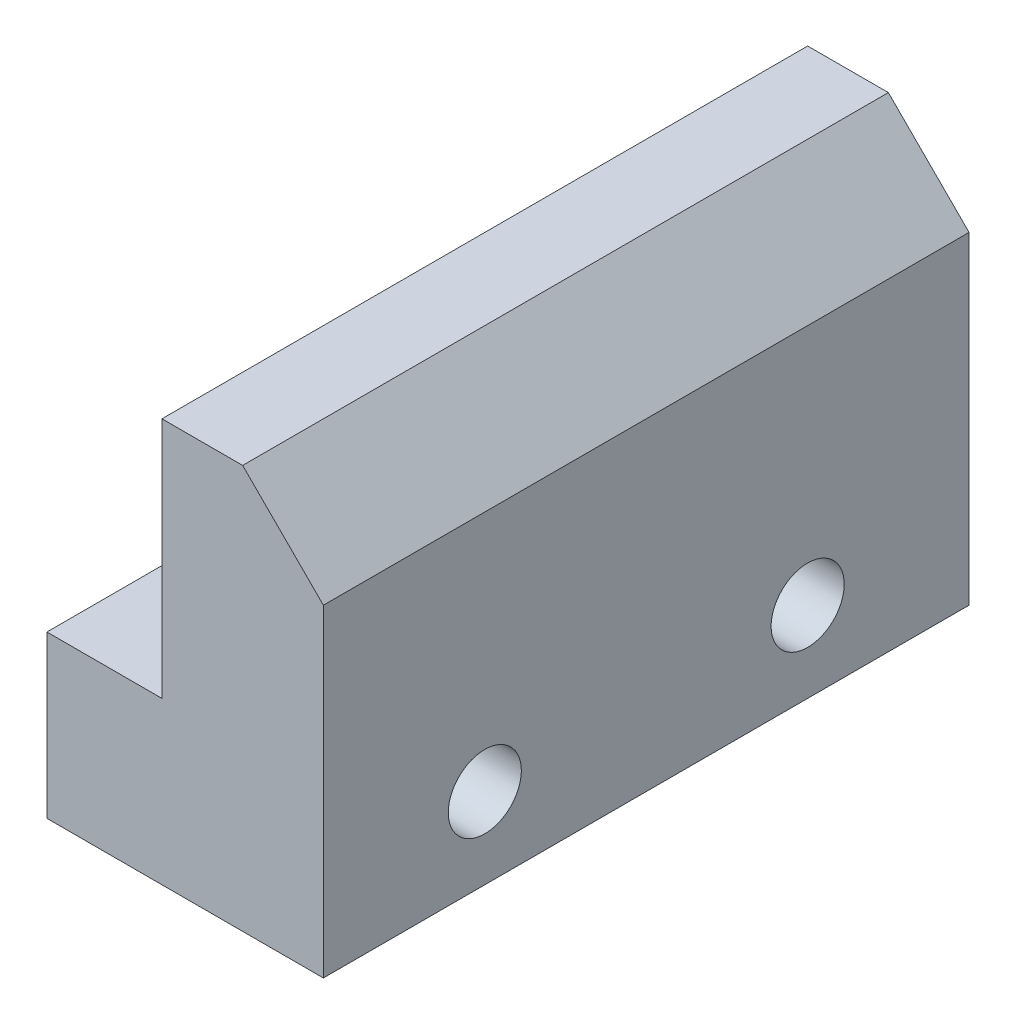
SolidWorks part; units mm, degrees
material "PETG"
ref_plane "Front Plane" through (0, 0, 0) normal (0, 0, 1) x (1, 0, 0)
ref_plane "Top Plane" through (0, 0, 0) normal (0, 1, 0) x (1, 0, 0)
ref_plane "Right Plane" through (0, 0, 0) normal (1, 0, 0) x (0, 0, -1)
sketch "Sketch1" plane through (0, 0, 0) normal (0, 0, 1) x (1, 0, 0)
  line L0 (18.1, 63.5) -> (43.5, 38.1)
  line L1 (0, -12.7) -> (43.5, -12.7)
  line L2 (0, -12.7) -> (0, 12.7)
  line L3 (0, 12.7) -> (18.1, 12.7)
  line L6 (18.1, 63.5) -> (18.1, 12.7)
  line L8 (43.5, 38.1) -> (43.5, -12.7)
  line L9 (18.1, 50.8) -> (30.8, 50.8)
  dimension "D1" = 25.4
  dimension "D2" = 43.5
  dimension "D3" = 50.8
  dimension "D4" = 25.4
  dimension "D5" = 25.4
extrude "Boss-Extrude1" add sketch "Sketch1" along normal mid plane 101.6 contours L9 L6 L3 L2 L1 L8 L0 region at (25.4375, 13.5394, 0)
sketch "Sketch2" plane through (43.5, 0, 0) normal (1, 0, 0) x (0, 0, -1)
  line L0 (-25.4, 0) -> (0, 0) construction
  line L1 (0, 0) -> (25.4, 0) construction
  line L2 (-50.8, 38.1) -> (-50.8, -12.7) construction
  circle A0 centre (-25.4, 0) radius 3.25
  circle A1 centre (25.4, 0) radius 3.25
  dimension "D1" = 25.4
  dimension "D2" = 6.5
extrude "Cut-Extrude1" cut sketch "Sketch2" against normal through all
sketch "Sketch3" plane through (43.5, 0, 0) normal (1, 0, 0) x (0, 0, -1)
  circle A0 centre (-25.4, 0) radius 5.75
  circle A1 centre (25.4, 0) radius 5.75
  dimension "D1" = 11.5
extrude "Cut-Extrude2" cut sketch "Sketch3" against normal offset from surface (33.5 mm away) 10 up to face at (0, 3.25, 25.4)
